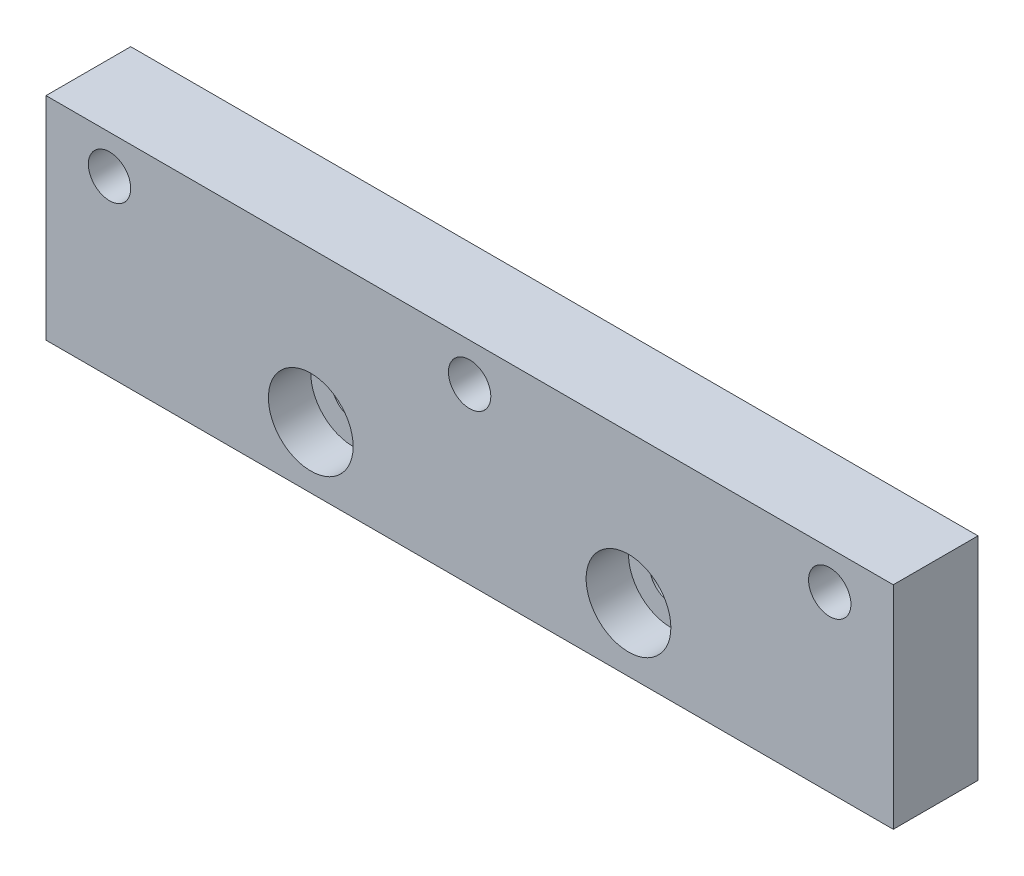
SolidWorks part; units mm, degrees
material "1060 Alloy"
ref_plane "Front Plane" through (0, 0, 0) normal (0, 0, 1) x (1, 0, 0)
ref_plane "Top Plane" through (0, 0, 0) normal (0, 1, 0) x (1, 0, 0)
ref_plane "Right Plane" through (0, 0, 0) normal (1, 0, 0) x (0, 0, -1)
sketch "Sketch2" plane through (0, 0, 0) normal (0, 0, 1) x (1, 0, 0)
  line L1 (-20, 5) -> (20, 5)
  line L2 (-20, 5) -> (-20, -5)
  line L3 (-20, -5) -> (20, -5)
  line L4 (20, 5) -> (20, -5)
  line L5 (-20, 5) -> (20, -5) construction
  line L6 (-20, -5) -> (20, 5) construction
  point P0 (0, 0)
  dimension "D1" = 10
  dimension "D2" = 40
extrude "Boss-Extrude1" add sketch "Sketch2" along normal blind 4
sketch "Sketch3" plane through (0, 0, 4) normal (0, 0, 1) x (1, 0, 0)
  line L1 (0, 5) -> (0, -5) construction
  line L2 (20, 5) -> (-20, 5) construction
  line L3 (-20, -5) -> (20, -5) construction
  line L4 (-7.5, -2) -> (7.5, -2) construction
  circle A0 centre (-17, 3.2) radius 1
  circle A1 centre (0, 3.2) radius 1
  circle A2 centre (17, 3.2) radius 1
  circle A3 centre (-7.5, -2) radius 1
  circle A4 centre (7.5, -2) radius 1
  point P19 (0, -2)
  dimension "D1" = 2
  dimension "D2" = 2
  dimension "D3" = 2
  dimension "D6" = 2
  dimension "D7" = 2
  dimension "D4" = 17
  dimension "D5" = 17
  dimension "D8" = 15
  dimension "D9" = 3
extrude "Cut-Extrude1" cut sketch "Sketch3" against normal through all
sketch "Sketch4" plane through (0, 0, 4) normal (0, 0, 1) x (1, 0, 0)
  circle A0 centre (-7.5, -2.1) radius 2
  circle A1 centre (7.5, -2) radius 2
  dimension "D1" = 4
  dimension "D2" = 4
extrude "Cut-Extrude2" cut sketch "Sketch4" against normal blind 2
